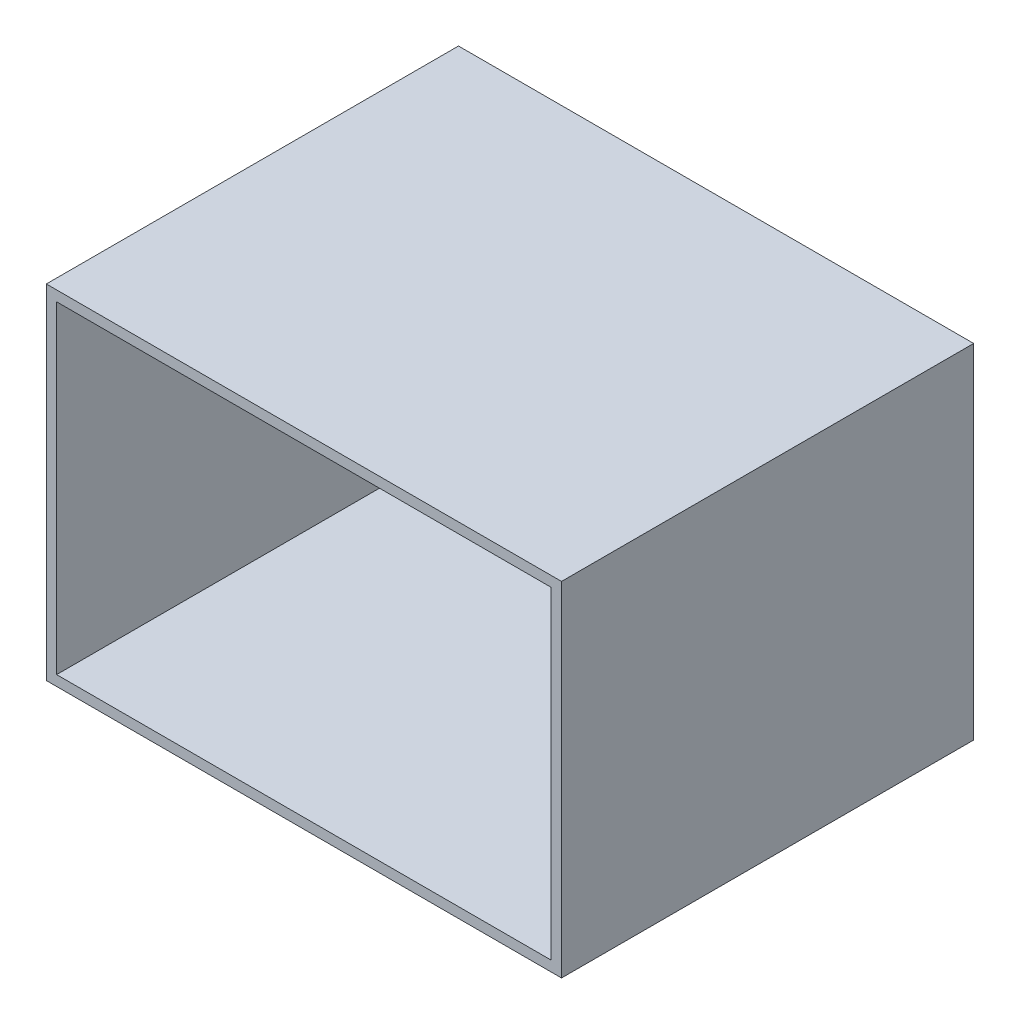
SolidWorks part; units mm, degrees
ref_plane "Plan de face" through (0, 0, 0) normal (0, 0, 1) x (1, 0, 0)
ref_plane "Plan de dessus" through (0, 0, 0) normal (0, 1, 0) x (1, 0, 0)
ref_plane "Plan de droite" through (0, 0, 0) normal (1, 0, 0) x (0, 0, -1)
sketch "Esquisse1" plane through (0, 0, 0) normal (0, 0, 1) x (1, 0, 0)
  line L1 (-75, 48.3756) -> (75, 48.3756)
  line L2 (-75, 48.3756) -> (-75, -51.6244)
  line L3 (-75, -51.6244) -> (75, -51.6244)
  line L4 (75, 48.3756) -> (75, -51.6244)
  point P4 (-75, -1.6244)
  dimension "D1" = 150
  dimension "D2" = 100
  dimension "D3" = 75
extrude "Boss.-Extru.1" add sketch "Esquisse1" along normal blind 120
sketch "Esquisse2" plane through (0, 0, 120) normal (0, 0, 1) x (1, 0, 0)
  line L0 (-75, 48.3756) -> (-75, -51.6244) construction
  line L1 (-72, 45.3756) -> (72, 45.3756)
  line L2 (-72, 45.3756) -> (-72, -48.6244)
  line L3 (-72, -48.6244) -> (72, -48.6244)
  line L4 (72, 45.3756) -> (72, -48.6244)
  line L5 (75, -51.6244) -> (75, 48.3756) construction
  line L6 (75, 48.3756) -> (-75, 48.3756) construction
  line L7 (-75, -51.6244) -> (75, -51.6244) construction
  dimension "D1" = 3
  dimension "D2" = 3
  dimension "D3" = 3
  dimension "D4" = 3
sketch "Esquisse3" plane through (0, 0, 0) normal (0, 0, -1) x (-1, 0, 0)
extrude "Enlèv. mat.-Extru.1" cut sketch "Esquisse2" against normal blind 117
sketch "Esquisse10" plane through (0, 48.3756, 0) normal (0, 1, 0) x (1, 0, 0)
